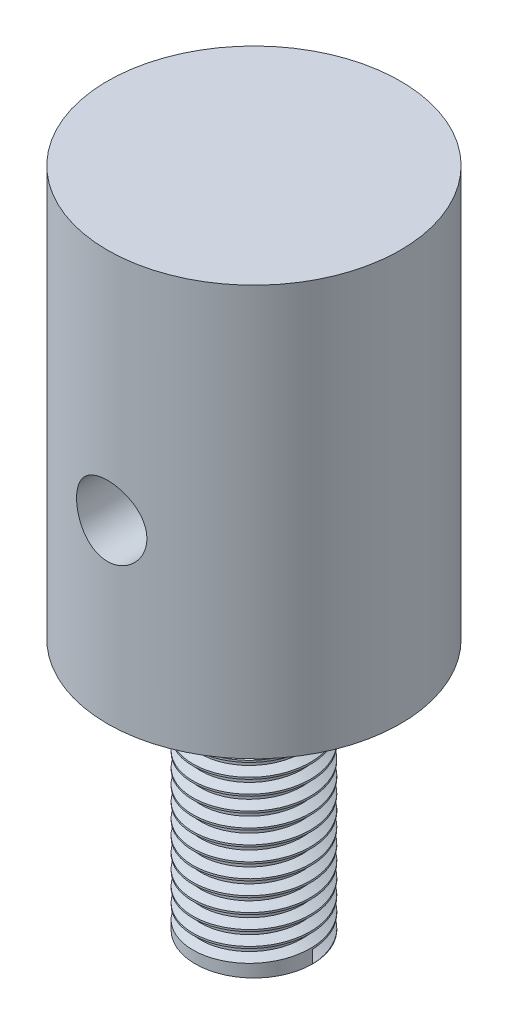
SolidWorks part; units mm, degrees
ref_plane "Front Plane" through (0, 0, 0) normal (0, 0, 1) x (1, 0, 0)
ref_plane "Top Plane" through (0, 0, 0) normal (0, 1, 0) x (1, 0, 0)
ref_plane "Right Plane" through (0, 0, 0) normal (1, 0, 0) x (0, 0, -1)
sketch "Sketch1" plane through (0, 0, 0) normal (0, 1, 0) x (1, 0, 0)
  circle A0 centre (0, 0) radius 2.5
  dimension "D1" = 5
extrude "Boss-Extrude1" add sketch "Sketch1" along normal blind 7
sketch "Sketch2" plane through (0, 0, 0) normal (0, 0, 1) x (1, 0, 0)
  line L0 (0, 0) -> (0, 3) construction
  line L1 (-2.5, 0) -> (2.5, 0) construction
  circle A0 centre (0, 3) radius 0.6
  dimension "D2" = 1.2
  dimension "D1" = 3
extrude "Cut-Extrude1" cut sketch "Sketch2" against normal through all both and the other way through all
sketch "Sketch3" plane through (0, 0, 0) normal (0, -1, 0) x (1, 0, 0)
  circle A0 centre (0, 0) radius 1
  dimension "D1" = 2
extrude "Boss-Extrude2" add sketch "Sketch3" along normal blind 4.3
thread "Thread1" pitch 0.25 method cut profile "Thread Profile1" start angle 0, offset 0, length 0, pitch 0.25, diameter 2
ref_plane "Plane1" through (1, -4.3, 0) normal (0, 0, 1) x (1, 0, 0)
sketch "Thread Profile1" plane through (1, -4.3, 0) normal (0, 0, 1) x (1, 0, 0)
  line L0 (0, 0) -> (0, 0.25) construction
  line L11 (0, 0) -> (0, 0.2187)
  line L12 (0, 0.2187) -> (-0.1353, 0.1406)
  line L13 (-0.1353, 0.1406) -> (-0.1353, 0.0781)
  line L15 (-0.1353, 0.0781) -> (0, 0)
  line L17 (-0.1353, 0.1094) -> (0, 0.1094) construction
  point P2 (0, 0)
  dimension "Pitch" = 0.25
  dimension "Profile_Angle" = 60
  dimension "Profile_Land" = 0.0625
  dimension "Profile_Height" = 0.1353
